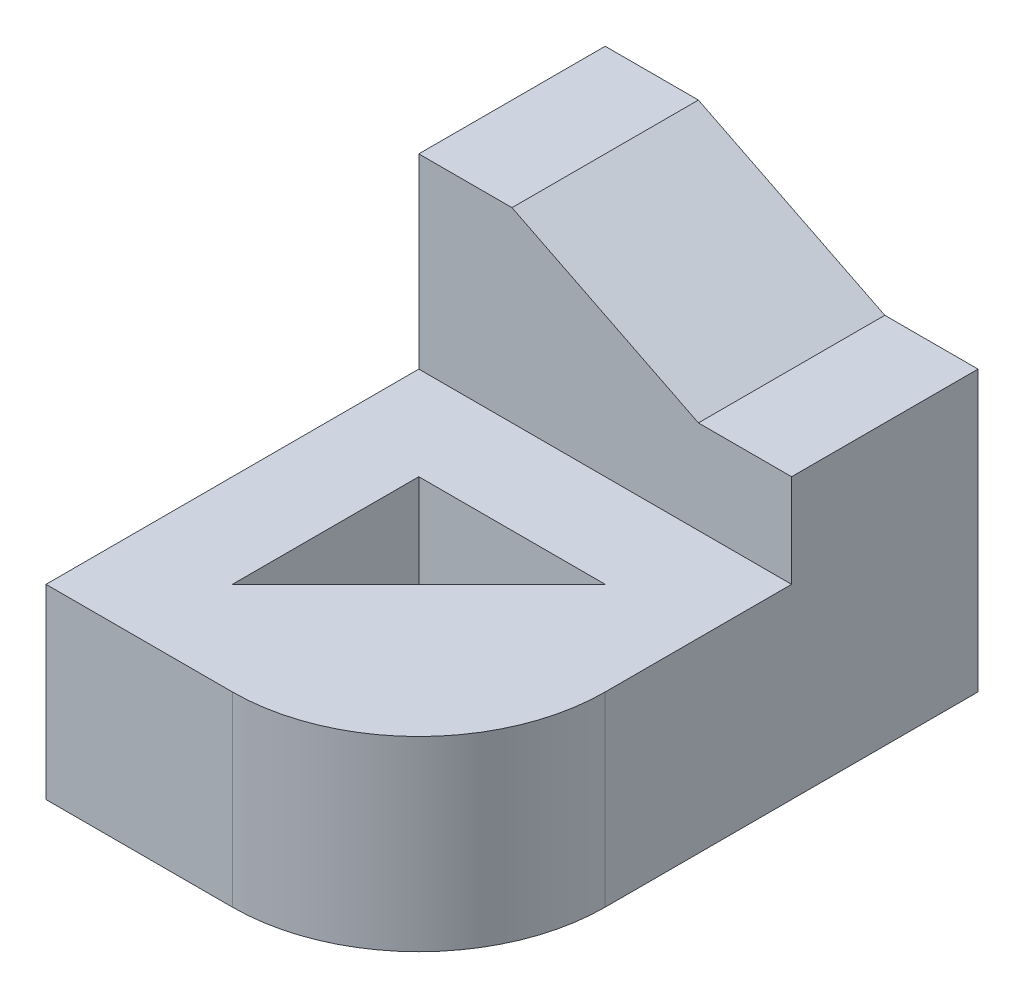
SolidWorks part; units mm, degrees
ref_plane "前基準面" through (0, 0, 0) normal (0, 0, 1) x (1, 0, 0)
ref_plane "上基準面" through (0, 0, 0) normal (0, 1, 0) x (1, 0, 0)
ref_plane "右基準面" through (0, 0, 0) normal (1, 0, 0) x (0, 0, -1)
sketch "草圖1" plane through (0, 0, 0) normal (0, 1, 0) x (1, 0, 0)
  line L0 (5, 5) -> (-5, -5)
  line L1 (-10, 10) -> (10, 10)
  line L2 (-10, 10) -> (-10, -10)
  line L3 (-10, -10) -> (10, -10)
  line L4 (10, 10) -> (10, -10)
  line L5 (-10, 10) -> (10, -10) construction
  line L6 (-10, -10) -> (10, 10) construction
  line L7 (-10, 10) -> (10, 10)
  line L8 (-10, 10) -> (-10, 20)
  line L9 (-10, 20) -> (10, 20)
  line L10 (10, 10) -> (10, 20)
  line L11 (10, 20) -> (5, 20)
  line L12 (10, 20) -> (10, 10)
  line L13 (10, 10) -> (5, 10)
  line L14 (5, 20) -> (5, 10)
  line L15 (-10, 10) -> (-5, 10)
  line L16 (-10, 10) -> (-10, 20)
  line L17 (-10, 20) -> (-5, 20)
  line L18 (-5, 10) -> (-5, 20)
  line L19 (-5, 5) -> (5, 5)
  line L20 (-5, 5) -> (-5, -5)
  line L23 (-5, 5) -> (5, -5) construction
  line L24 (-5, -5) -> (5, 5) construction
  point P0 (0, 0)
  point P12 (0, 0)
  dimension "D1" = 20
  dimension "D2" = 20
  dimension "D3" = 10
  dimension "D4" = 10
  dimension "D5" = 5
  dimension "D6" = 5
  dimension "D7" = 10
extrude "填料-伸長1" add sketch "草圖1" along normal blind 10 contours L4 L7 L1 L2 L3 L20 L19 L0 region at (0.2381, 0, 0.2381)
extrude "填料-伸長2" add sketch "草圖1<3>" along normal blind 20 contours L1 L18 L9 L8 | L18 L7 L14 L9 | L9 L14 L7 L10 region at (-7.5, 0, -15) region at (0, 0, -15) region at (7.5, 0, -15)
sketch "草圖1<3>" plane through (0, 0, 0) normal (0, 1, 0) x (1, 0, 0) same geometry as "草圖1"
sketch "草圖2" plane through (0, 0, -10) normal (0, 0, 1) x (1, 0, 0)
  line L0 (-5, 20) -> (5, 15)
  line L1 (-10, 20) -> (10, 20) construction
  line L2 (5, 15) -> (5, 20)
  line L3 (5, 15) -> (10, 15)
  line L4 (10, 20) -> (10, 10) construction
  line L5 (-5, 20) -> (10, 20)
  line L6 (10, 20) -> (10, 15)
  line M5 (10, 10) -> (10, 20)
  line M6 (10, 20) -> (-10, 20)
  dimension "D1" = 5
  dimension "D2" = 5
  dimension "D3" = 5
extrude "除料-伸長1" cut sketch "草圖2" against normal blind 20 contours L0 L2 M6 | L2 L3 M5 M6 region at (1.6667, 18.3333, -10) region at (7.5, 17.5, -10)
fillet "圓角1" radius 10 1 edges at (10, 5, 10)
